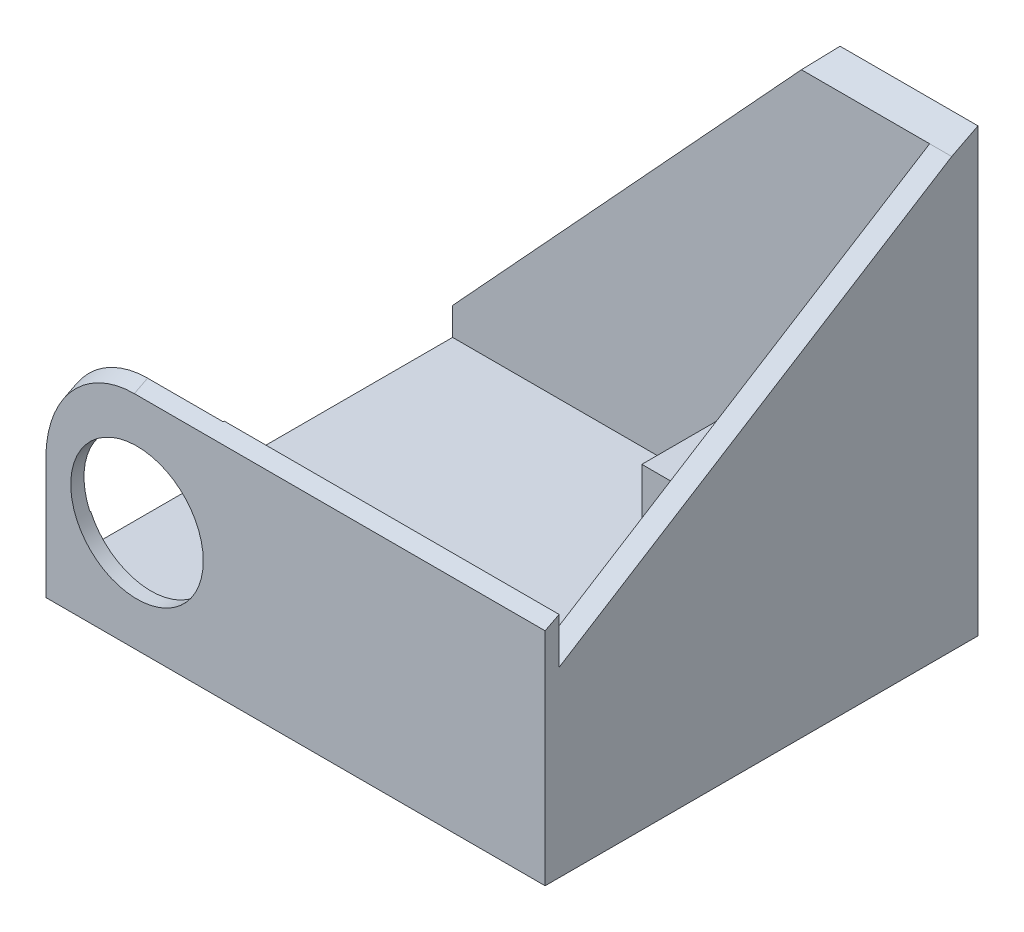
SolidWorks part; units mm, degrees
ref_plane "Front Plane" through (0, 0, 0) normal (0, 0, 1) x (1, 0, 0)
ref_plane "Top Plane" through (0, 0, 0) normal (0, 1, 0) x (1, 0, 0)
ref_plane "Right Plane" through (0, 0, 0) normal (1, 0, 0) x (0, 0, -1)
sketch "Sketch1" plane through (0, 0, 0) normal (0, 1, 0) x (1, 0, 0)
  line L1 (-47.3731, 20.2038) -> (65.6269, 20.2038)
  line L2 (-47.3731, 20.2038) -> (-47.3731, -77.7962)
  line L3 (-47.3731, -77.7962) -> (65.6269, -77.7962)
  line L4 (65.6269, 20.2038) -> (65.6269, -77.7962)
  dimension "D1" = 113
  dimension "D2" = 98
extrude "Boss-Extrude1" add sketch "Sketch1" against normal blind 100
sketch "Sketch2" plane through (65.6269, 0, 0) normal (1, 0, 0) x (0, 0, -1)
  line L0 (20.2038, 0) -> (-77.7962, -50)
  line L1 (-77.7962, -100) -> (-77.7962, 0) construction
  line L2 (-77.7962, -50) -> (-77.7962, 0)
  line L3 (-77.7962, 0) -> (20.2038, 0)
extrude "Cut-Extrude1" cut sketch "Sketch2" against normal blind 130
sketch "Sketch3" plane through (0, 0, -20.2038) normal (0, 0, -1) x (-1, 0, 0)
  line L0 (-34.3973, 0) -> (47.3731, -88.7322)
  line L1 (-65.6269, 0) -> (47.3731, 0) construction
  line L2 (47.3731, -100) -> (47.3731, 0) construction
  line L3 (47.3731, -88.7322) -> (47.3731, 0)
  line L4 (47.3731, 0) -> (-34.3973, 0)
extrude "Cut-Extrude3" cut sketch "Sketch3" against normal blind 95
sketch "Sketch4" plane through (0, 0, 0) normal (0, 1, 0) x (1, 0, 0)
  line L0 (-47.3731, -74.7962) -> (-47.3731, 20.2038) construction
  line L1 (-47.3731, 14.2533) -> (65.6269, 14.2533)
  line L2 (-47.3731, 14.2533) -> (-47.3731, -74.6229)
  line L3 (-47.3731, -74.6229) -> (65.6269, -74.6229)
  line L4 (65.6269, 14.2533) -> (65.6269, -74.6229)
  line L5 (65.6269, -77.7962) -> (65.6269, 20.2038) construction
extrude "Cut-Extrude4" cut sketch "Sketch4" against normal blind 95
sketch "Sketch6" plane through (65.6269, 0, 0) normal (1, 0, 0) x (0, 0, -1)
  line L0 (14.2533, -95) -> (14.2533, -3.036)
  line L2 (-74.6229, -58.7384) -> (-74.6229, -95)
  line L3 (-74.6229, -95) -> (14.2533, -95)
  line L4 (14.2533, -3.036) -> (-74.6229, -58.7384)
extrude "Boss-Extrude4" add sketch "Sketch6" against normal blind 5
sketch "Sketch7" plane through (0, -95, 0) normal (0, 1, 0) x (1, 0, 0)
  line L0 (60.6269, 14.2533) -> (-47.3731, 14.2533) construction
  line L1 (23.9396, 14.2533) -> (60.6269, 14.2533)
  line L2 (23.9396, 14.2533) -> (23.9396, -14.2149)
  line L3 (23.9396, -14.2149) -> (60.6269, -14.2149)
  line L4 (60.6269, 14.2533) -> (60.6269, -14.2149)
  line L5 (60.6269, 14.2533) -> (60.6269, -74.6229) construction
extrude "Boss-Extrude6" add sketch "Sketch7" along normal blind 25
sketch "Sketch8" plane through (0, 0, 77.7962) normal (0, 0, 1) x (1, 0, 0)
  circle A0 centre (-26.7712, -75) radius 15
  dimension "D1" = 30
extrude "Cut-Extrude5" cut sketch "Sketch8" against normal blind 25
fillet "Fillet1" radius 20 1 edges at (-47.3731, -49.2347, 76.2962)
